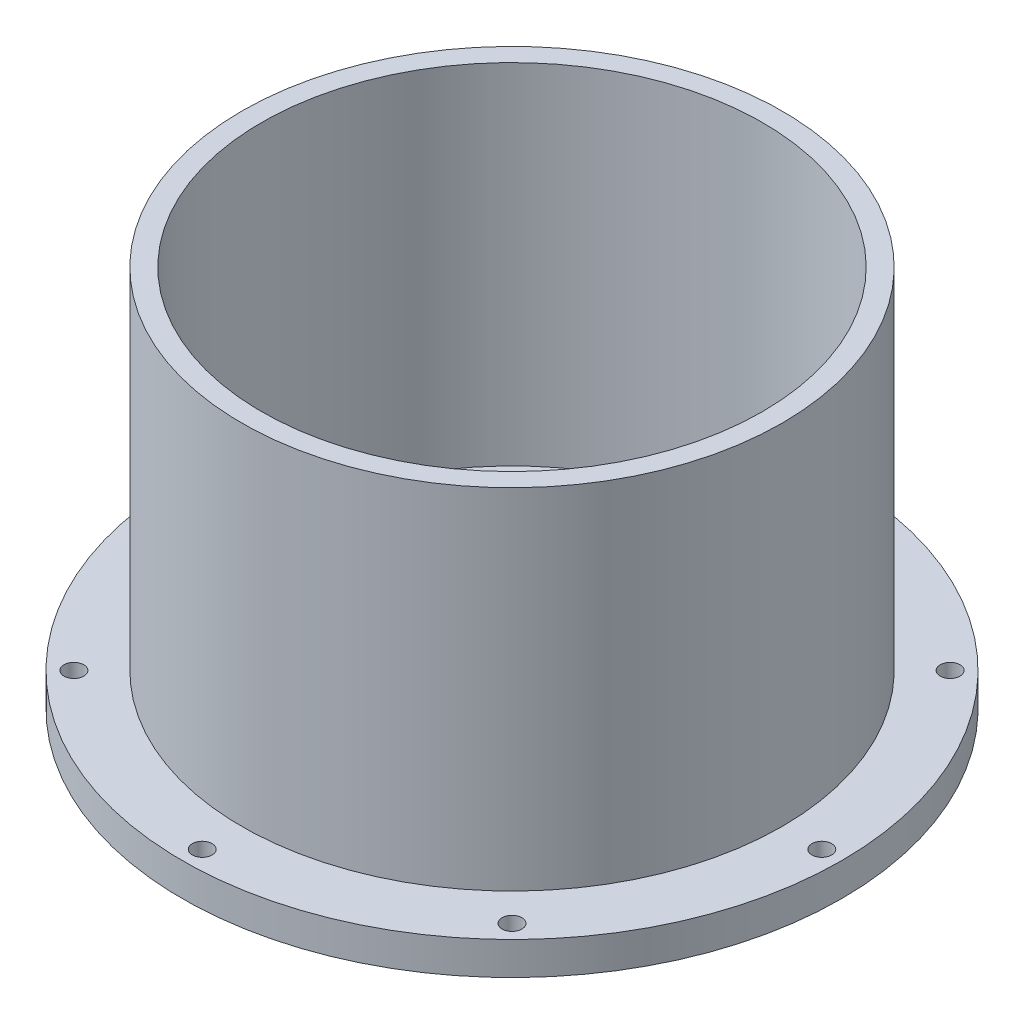
SolidWorks part; units mm, degrees
ref_plane "Front Plane" through (0, 0, 0) normal (0, 0, 1) x (1, 0, 0)
ref_plane "Top Plane" through (0, 0, 0) normal (0, 1, 0) x (1, 0, 0)
ref_plane "Right Plane" through (0, 0, 0) normal (1, 0, 0) x (0, 0, -1)
sketch "Sketch2" plane through (0, 0, 0) normal (0, 0, 1) x (1, 0, 0)
  line L0 (0, 5) -> (0, 0)
  line L1 (0, 0) -> (50, 0)
  line L2 (50, 0) -> (50, 5)
  line L3 (50, 5) -> (41, 5)
  line L4 (41, 5) -> (41, 58)
  line L5 (41, 58) -> (38, 58)
  line L6 (38, 58) -> (38, 5)
  line L7 (38, 5) -> (0, 5)
  line L8 (0, 0) -> (0, 38.6828) construction
  dimension "D1" = 50
  dimension "D2" = 5
  dimension "D3" = 58
  dimension "D4" = 9
  dimension "D5" = 3
sketch "Sketch3" plane through (0, 0, 0) normal (0, 1, 0) x (1, 0, 0)
  line L0 (-13.5, 12) -> (-13.5, 4) construction
  line L1 (13.5, 12) -> (13.5, 4) construction
  line L2 (-13.5, 12) -> (-13.5, 20) construction
  line L3 (0, 0) -> (0, -47) construction
  circle A0 centre (-13.5, 12) radius 1
  circle A1 centre (13.5, 12) radius 1
  circle A2 centre (-13.5, 4) radius 1
  circle A3 centre (-13.5, -4) radius 1
  circle A4 centre (13.5, 4) radius 1
  circle A5 centre (13.5, -4) radius 1
  circle A6 centre (-13.5, 20) radius 1
  circle A7 centre (13.5, 20) radius 1
  circle A8 centre (0, -47) radius 1.5
  circle A9 centre (0, 0) radius 47 construction
  circle A10 centre (-33.234, -33.234) radius 1.5
  circle A11 centre (-47, 0) radius 1.5
  circle A12 centre (-33.234, 33.234) radius 1.5
  circle A13 centre (0, 47) radius 1.5
  circle A14 centre (33.234, 33.234) radius 1.5
  circle A15 centre (47, 0) radius 1.5
  circle A16 centre (33.234, -33.234) radius 1.5
  circle A18 centre (0, 26.5) radius 12.5 construction
  circle A19 centre (0, -11) radius 25 construction
  dimension "D1" = 2
  dimension "D11" = 3
  dimension "D12" = 94
  dimension "D14" = 50
  dimension "D15" = 25
  dimension "D2" = 27
  dimension "D3" = 13.5
  dimension "D4" = 12
  dimension "D6" = 8
  dimension "D8" = 8
  dimension "D10" = 8
  dimension "D16" = 6.5
  dimension "D5" = 3
  dimension "D7" = 3
  dimension "D9" = 2
  dimension "D13" = 8
revolve "Revolve1" add sketch "Sketch2" angle 360 about L8
extrude "Cut-Extrude2" cut sketch "Sketch3" along normal blind 10
